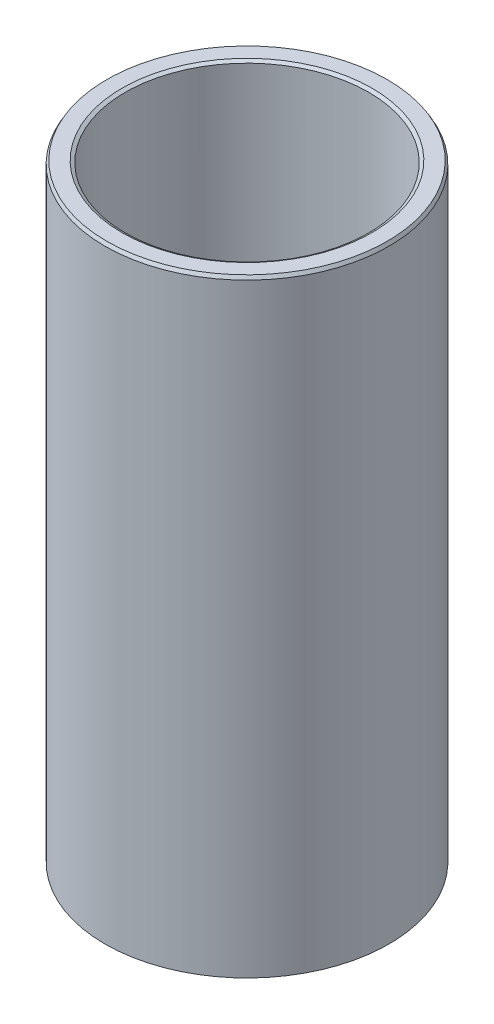
SolidWorks part; units mm, degrees
ref_plane "Front Plane" through (0, 0, 0) normal (0, 0, 1) x (1, 0, 0)
ref_plane "Top Plane" through (0, 0, 0) normal (0, 1, 0) x (1, 0, 0)
ref_plane "Right Plane" through (0, 0, 0) normal (1, 0, 0) x (0, 0, -1)
sketch "Sketch1" plane through (0, 0, 0) normal (0, 1, 0) x (1, 0, 0)
  circle A0 centre (0, 0) radius 55
  dimension "SLEEVE_OD" = 110
extrude "Boss-Extrude1" add sketch "Sketch1" along normal blind 236.0087
sketch "Sketch2" plane through (0, 0, 0) normal (0, 1, 0) x (1, 0, 0)
  circle A0 centre (0, 0) radius 47.1597
  dimension "BORE_D" = 94.3194
extrude "Cut-Extrude1" cut sketch "Sketch2" along normal through all
chamfer "Chamfer1" distance 1.2695 angle 30 4 edges at (0, 236.0087, 47.1597) (0, 0, 47.1597) (0, 0, 55) (0, 236.0087, 55) first distance on face at (0, 236.0087, 47.1597) first distance on face at (0, 0, 47.1597) first distance on face at (0, 236.0087, 55)
